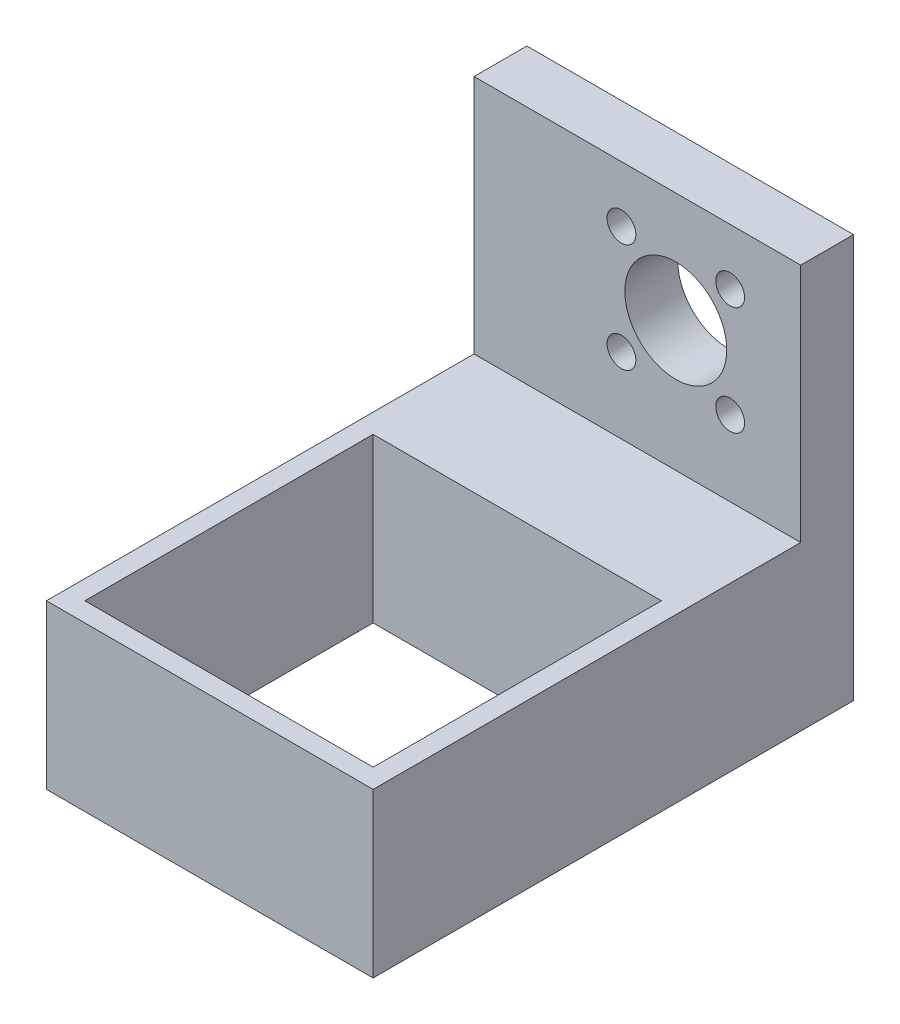
SolidWorks part; units mm, degrees
ref_plane "Płaszczyzna przednia" through (0, 0, 0) normal (0, 0, 1) x (1, 0, 0)
ref_plane "Płaszczyzna górna" through (0, 0, 0) normal (0, 1, 0) x (1, 0, 0)
ref_plane "Płaszczyzna prawa" through (0, 0, 0) normal (1, 0, 0) x (0, 0, -1)
sketch "Szkic1" plane through (0, 0, 0) normal (0, 1, 0) x (1, 0, 0)
  line L1 (-17, 25) -> (17, 25)
  line L2 (-17, 25) -> (-17, -25)
  line L3 (-17, -25) -> (17, -25)
  line L4 (17, 25) -> (17, -25)
  line L5 (-17, 25) -> (17, -25) construction
  line L6 (-17, -25) -> (17, 25) construction
  point P0 (0, 0)
  dimension "D1" = 34
  dimension "D2" = 50
extrude "Dodanie-wyciągnięcie1" add sketch "Szkic1" along normal blind 17
sketch "Szkic2" plane through (0, 17, 0) normal (0, 1, 0) x (1, 0, 0)
  line L0 (0, 25) -> (0, -25) construction
  line L1 (17, 25) -> (-17, 25) construction
  line L2 (-17, -25) -> (17, -25) construction
  line L3 (-17, 25) -> (-17, -25) construction
  line L4 (15, 7) -> (-15, 7)
  line L5 (15, 7) -> (15, -23)
  line L6 (15, -23) -> (-15, -23)
  line L7 (-15, 7) -> (-15, -23)
  line L8 (15, 7) -> (-15, -23) construction
  line L9 (15, -23) -> (-15, 7) construction
  point P6 (0, -8)
  dimension "D1" = 2
  dimension "D2" = 2
  dimension "D3" = 30
extrude "Wytnij-wyciągnięcie1" cut sketch "Szkic2" against normal blind 20
sketch "Szkic3" plane through (0, 17, 0) normal (0, 1, 0) x (1, 0, 0)
  line L0 (17, -25) -> (17, 25) construction
  line L1 (17, 25) -> (-17, 25)
  line L2 (17, 25) -> (17, 19.5)
  line L3 (17, 19.5) -> (-17, 19.5)
  line L4 (-17, 25) -> (-17, 19.5)
  line L5 (17, 25) -> (-17, 25) construction
  line L6 (-17, 25) -> (-17, -25) construction
  line L7 (-17, -25) -> (17, -25) construction
  dimension "D1" = 44.5
extrude "Dodanie-wyciągnięcie2" add sketch "Szkic3" along normal blind 25
sketch "Szkic4" plane through (0, 0, -25) normal (0, 0, -1) x (-1, 0, 0)
  line L1 (-4, 30.5) -> (-9.6569, 36.1569) construction
  line L2 (-4, 30.5) -> (-4, 38.5) construction
  line L3 (-17, 42) -> (17, 42) construction
  line L4 (0, 0) -> (0, 62.7345) construction
  line L6 (-17, 0) -> (17, 0) construction
  circle A0 centre (1.6569, 36.1569) radius 1.5
  circle A1 centre (-4, 30.5) radius 5.3
  circle A2 centre (-4, 30.5) radius 8
  circle A3 centre (-9.6569, 36.1569) radius 1.5
  circle A4 centre (-4, 30.5) radius 8
  circle A5 centre (1.6569, 24.8431) radius 1.5
  circle A6 centre (-4, 30.5) radius 8
  circle A7 centre (-9.6569, 24.8431) radius 1.5
  circle A8 centre (-4, 30.5) radius 8
  point P21 (-4, 30.5)
  dimension "D1" = 4
  dimension "D2" = 11.5
  dimension "D3" = 10.6
  dimension "D4" = 16
  dimension "D5" = 3
  dimension "D6" = 45
  dimension "D7" = 4
extrude "Wytnij-wyciągnięcie2" cut sketch "Szkic4" against normal blind 25 contours A2 A3 | A2 A3 | A2 A0 | A0 A2 | A6 A7 | A6 A7 | A4 A5 | A4 A5 | A1 region at (-2.0886, 36.5886, -25) region at (-1.1893, 35.6893, -25) region at (9.1893, 35.6893, -25) region at (10.0886, 36.5886, -25) region at (-2.0886, 24.4114, -25) region at (-1.1893, 25.3107, -25) region at (9.1893, 25.3107, -25) region at (10.0886, 24.4114, -25) region at (4, 30.5, -25)
